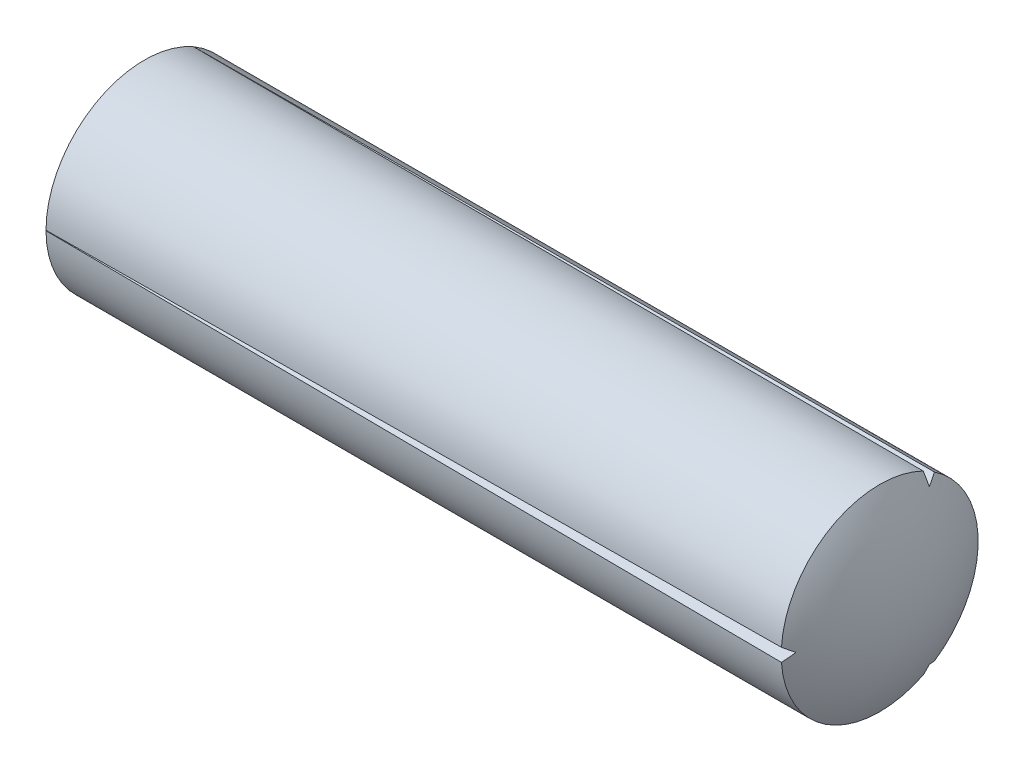
SolidWorks part; units mm, degrees
ref_plane "Plane1" through (0, 0, 0) normal (0, 0, 1) x (1, 0, 0)
ref_plane "Plane2" through (0, 0, 0) normal (0, 1, 0) x (1, 0, 0)
ref_plane "Plane3" through (0, 0, 0) normal (1, 0, 0) x (0, 0, -1)
sketch "Sketch1" plane through (0, 0, 0) normal (0, 0, 1) x (1, 0, 0)
  line L0 (-40, 0) -> (40, 0) construction
  line L1 (-100, 0) -> (-100, 1.25)
  line L2 (-96.6819, 12.5) -> (-3.3494, 12.5)
  line L4 (0, 0) -> (-100, 0)
  arc A0 (-96.6819, 12.5) -> (-100, 1.25) centre (-75.0313, 0) ccw
  arc A1 (0, 0) -> (-3.3494, 12.5) centre (-25, 0) ccw
  dimension "D2" = 25
  dimension "D3" = 2.5
revolve "Base-Revolve" add sketch "Sketch1" angle 360 about L0
sketch "Sketch2" plane through (0, 0, 0) normal (1, 0, 0) x (0, 0, -1)
  line L0 (0, 0) -> (-15, 0) construction
  line L1 (-11.25, 0) -> (-12.5, 0.8753)
  line L2 (-11.25, 0) -> (-12.5, -0.8753)
  line L3 (-12.5, -0.8753) -> (-12.5, 0.8753)
  circle A0 centre (0, 0) radius 11.25 construction
  circle A1 centre (0, 0) radius 12.5 construction
  dimension "D1" = 22.5
  dimension "D2" = 70
  dimension "D3" = 35
sketch "Sketch4" plane through (0, 0, 0) normal (0, 1, 0) x (1, 0, 0)
  line L0 (-110, 0) -> (10, 0) construction
  line L1 (-40, 0) -> (40, 0) construction
  line L2 (0, -11.25) -> (-100, -12.5)
  dimension "D1" = 22.5
  dimension "D2" = 100
  dimension "D3" = 25
sweep "Cut-Sweep1" cut profiles "Sketch2" path "Sketch4"
pattern_circular "CirPattern1" count 3 over 360 about axis through (-40, 0, 0) along (1, 0, 0) of "Cut-Sweep1"
equation "\"D1@Sketch1\" = \"Diameter@Sketch1\""
equation "\"D2@Sketch1\" = \"Diameter@Sketch1\""
equation "\"D3@Sketch1\" = \"Diameter@Sketch1\" * .1"
equation "\"D1@Sketch2\" = \"Diameter@Sketch1\" * .9"
equation "\"D3@Sketch2\" = \"D2@Sketch2\" / 2"
equation "\"D1@Sketch4\" = \"D1@Sketch2\""
equation "\"D2@Sketch4\" = \"Length@Sketch1\""
equation "\"D3@Sketch4\" = \"Diameter@Sketch1\""
